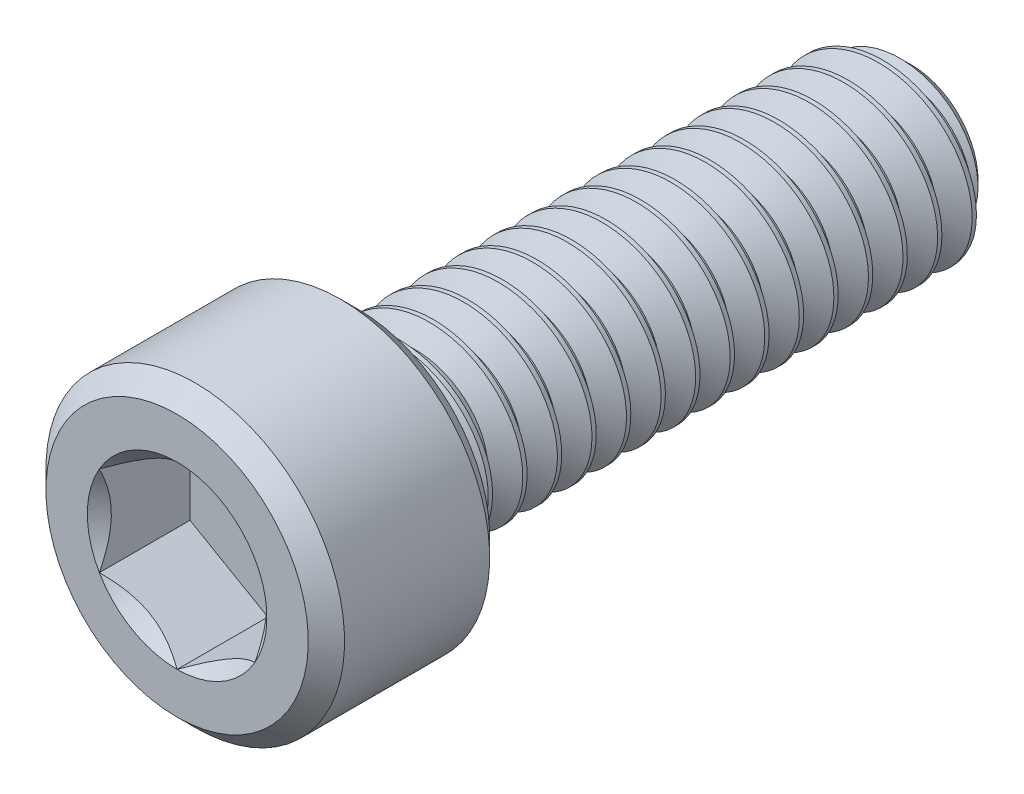
SolidWorks part; units mm, degrees
ref_plane "Front Plane" through (0, 0, 0) normal (0, 0, 1) x (1, 0, 0)
ref_plane "Top Plane" through (0, 0, 0) normal (0, 1, 0) x (1, 0, 0)
ref_plane "Right Plane" through (0, 0, 0) normal (1, 0, 0) x (0, 0, -1)
sketch "Sketch1" plane through (0, 0, 0) normal (1, 0, 0) x (0, 0, -1)
  line L0 (8.4328, 0) -> (-8.4328, 0) construction
  line L1 (-8.4328, 0) -> (-8.4328, 3.0124)
  line L2 (-8.4328, 3.0124) -> (-8.0162, 3.429)
  line L3 (-8.0162, 3.429) -> (-4.6838, 3.429)
  line L4 (-4.6838, 3.429) -> (-4.2672, 3.0124)
  line L5 (-4.2672, 3.0124) -> (-4.2672, 2.0828)
  line L6 (-4.2672, 2.0828) -> (7.8772, 2.0828)
  line L7 (7.8772, 2.0828) -> (8.4328, 1.5272)
  line L8 (8.4328, 1.5272) -> (8.4328, 0)
  line L9 (8.3832, 2.1687) -> (9.1769, 2.1687) construction
  line L10 (9.1769, 2.1687) -> (8.7801, 1.4813) construction
  line L11 (8.7801, 1.4813) -> (8.3832, 2.1687) construction
  line L12 (8.4328, 2.0828) -> (9.1273, 2.0828) construction
  line L13 (8.7801, 2.1687) -> (8.7801, 2.0828) construction
  line L14 (8.7305, 1.5672) -> (8.8297, 1.5672) construction
  line L15 (8.7801, 1.5672) -> (8.7801, 1.4813) construction
  line L16 (8.408, 2.1258) -> (9.1521, 2.1258)
  line L17 (9.1521, 2.1258) -> (8.8297, 1.5672)
  line L18 (8.8297, 1.5672) -> (8.7305, 1.5672)
  line L19 (8.7305, 1.5672) -> (8.408, 2.1258)
  line L20 (7.8772, -2.0828) -> (6.4484, -2.0828) construction
  point P4 (0, 0)
  point P25 (8.7801, 2.1258)
  point P26 (8.4328, 2.0828)
  point P33 (6.4484, -2.0828)
  dimension "Head Ht" = 4.1656
  dimension "Screw Size" = 4.1656
  dimension "Head Dia" = 6.858
  dimension "D1" = 45
  dimension "D2" = 45
  dimension "D3" = 0.4166
  dimension "D4" = 0.4166
  dimension "Pitch" = 0.7937
  dimension "D5" = 0.0992
  dimension "D6" = 0.5556
  dimension "D7" = 1.4287
  dimension "Length" = 12.7
sketch "Sketch2" plane through (0, 0, 0) normal (0, 0, 1) x (1, 0, 0)
  line L1 (0, 2.0622) -> (-1.7859, 1.0311)
  line L2 (-1.7859, 1.0311) -> (-1.7859, -1.0311)
  line L3 (-1.7859, -1.0311) -> (0, -2.0622)
  line L4 (0, -2.0622) -> (1.7859, -1.0311)
  line L5 (1.7859, -1.0311) -> (1.7859, 1.0311)
  line L6 (1.7859, 1.0311) -> (0, 2.0622)
  circle A0 centre (0, 0) radius 1.7859 construction
  circle A1 centre (0, 0) radius 3.429
  point P1 (0, 3.429)
  dimension "D1" = 6.858
  dimension "Drive Size" = 3.5719
sketch "Sketch3" plane through (0, 0, 0) normal (1, 0, 0) x (0, 0, -1)
  line L0 (8.4328, 0) -> (-8.4328, 0) construction
  line L1 (-8.4328, 0) -> (-8.4328, 3.0124) construction
  line L2 (-8.4328, 3.0124) -> (-8.0162, 3.429) construction
  line L3 (-8.0162, 3.429) -> (-4.6838, 3.429) construction
  line L4 (-4.6838, 3.429) -> (-4.2672, 3.0124) construction
  line L5 (-4.2672, 3.0124) -> (-4.2672, 2.0828) construction
  line L6 (-4.2672, 2.0828) -> (7.8772, 2.0828) construction
  line L7 (7.8772, 2.0828) -> (8.4328, 1.5272) construction
  line L8 (8.4328, 1.5272) -> (8.4328, 0) construction
  line L9 (8.4328, 0) -> (-8.4328, 0)
  line L10 (-8.4328, 0) -> (-8.4328, 3.0124)
  line L11 (-8.4328, 3.0124) -> (-8.0162, 3.429)
  line L12 (-8.0162, 3.429) -> (-4.6838, 3.429)
  line L13 (-4.6838, 3.429) -> (-4.2672, 3.0124)
  line L14 (-4.2672, 3.0124) -> (-4.2672, 2.0828)
  line L15 (-4.2672, 2.0828) -> (7.8772, 2.0828)
  line L16 (7.8772, 2.0828) -> (8.4328, 1.5272)
  line L17 (8.4328, 1.5272) -> (8.4328, 0)
revolve "Revolve1" add sketch "Sketch3" angle 360 about L0
sketch "Sketch4" plane through (0, 0, 8.4328) normal (0, 0, 1) x (1, 0, 0)
  line L0 (0, -2.0622) -> (1.7859, -1.0311) construction
  line L1 (1.7859, -1.0311) -> (1.7859, 1.0311) construction
  line L2 (1.7859, 1.0311) -> (0, 2.0622) construction
  line L3 (0, 2.0622) -> (-1.7859, 1.0311) construction
  line L4 (-1.7859, 1.0311) -> (-1.7859, -1.0311) construction
  line L5 (-1.7859, -1.0311) -> (0, -2.0622) construction
  line L6 (0, -2.0622) -> (1.7859, -1.0311)
  line L7 (1.7859, -1.0311) -> (1.7859, 1.0311)
  line L8 (1.7859, 1.0311) -> (0, 2.0622)
  line L9 (0, 2.0622) -> (-1.7859, 1.0311)
  line L10 (-1.7859, 1.0311) -> (-1.7859, -1.0311)
  line L11 (-1.7859, -1.0311) -> (0, -2.0622)
extrude "Cut-Extrude1" cut sketch "Sketch4" against normal blind 2.0828
sketch "Sketch5" plane through (0, 0, 8.4328) normal (0, 0, 1) x (1, 0, 0)
  circle A0 centre (0, 0) radius 2.0622
extrude "Cut-Extrude3" cut sketch "Sketch5" against normal through all draft 45
split "Split1" bodies to split 107 resulting bodies 108 109 split by face at (0, 3.0124, 4.2672)
sketch "Sketch6" plane through (0, 0, -8.4328) normal (0, 0, -1) x (-1, 0, 0)
  circle A0 centre (0, 0) radius 2.0828 construction
  circle A1 centre (0, 0) radius 2.0828
curve "Helix/Spiral1" pitch 0.7937 height 13.4937 radius 2.0828 centre (0, 0, -8.4328) axis (0, 0, 1) start towards (0, 1, 0)
sketch "Sketch7" plane through (0, 0, 0) normal (1, 0, 0) x (0, 0, -1)
  line L0 (8.408, 2.1258) -> (9.1521, 2.1258) construction
  line L1 (9.1521, 2.1258) -> (8.8297, 1.5672) construction
  line L2 (8.8297, 1.5672) -> (8.7305, 1.5672) construction
  line L3 (8.7305, 1.5672) -> (8.408, 2.1258) construction
  line L4 (8.408, 2.1258) -> (9.1521, 2.1258)
  line L5 (9.1521, 2.1258) -> (8.8297, 1.5672)
  line L6 (8.8297, 1.5672) -> (8.7305, 1.5672)
  line L7 (8.7305, 1.5672) -> (8.408, 2.1258)
sweep "Cut-Sweep1" cut profiles "Sketch7" path "Helix/Spiral1" align with end faces yes
sketch "Sketch8" plane through (0, 0, 4.2672) normal (0, 0, -1) x (-1, 0, 0)
  circle A1 centre (0, 0) radius 2.0828
extrude "Boss-Extrude1" add sketch "Sketch8" along normal up to next (12.7 mm away) draft 20
equation "\"D3@Sketch1\"=\"Head Ht@Sketch1\"/10"
equation "\"D4@Sketch1\"=\"Head Ht@Sketch1\"/10"
equation "\"D5@Sketch1\"=\"Pitch@Sketch1\"/8"
equation "\"D6@Sketch1\"=\"Pitch@Sketch1\"*.7"
equation "\"D7@Sketch1\"=\"Pitch@Sketch1\"*2.5-\"D6@Sketch1\""
equation "\"D1@Cut-Extrude1\"=\"Head Ht@Sketch1\"/2"
equation "\"D4@Helix/Spiral1\"=\"Pitch@Sketch1\""
equation "\"D3@Helix/Spiral1\"=\"Length@Sketch1\"+\"D4@Helix/Spiral1\""
